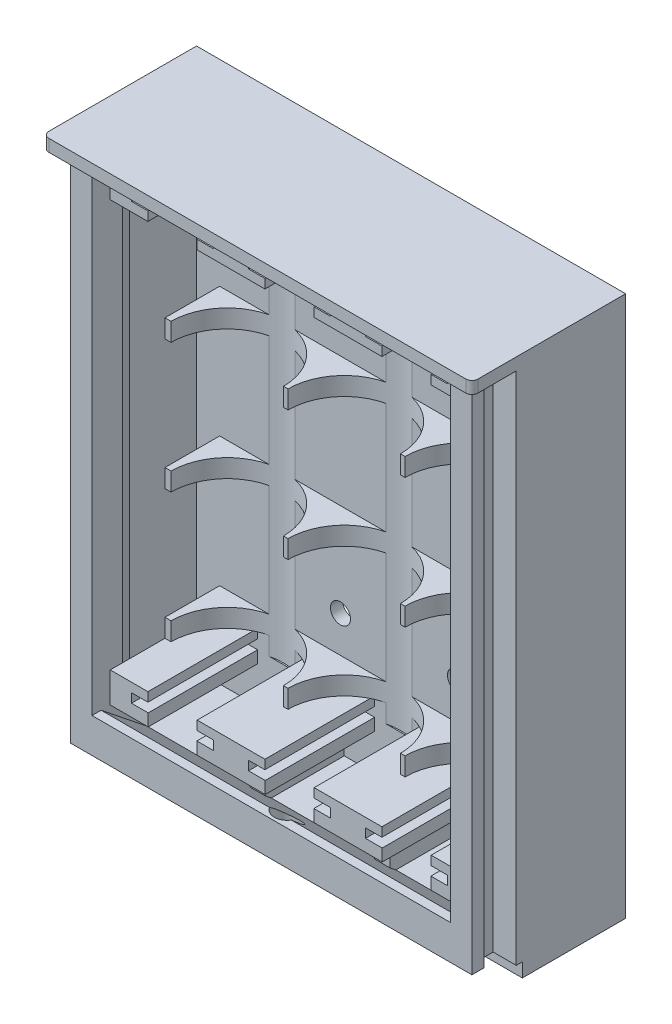
SolidWorks part; units mm, degrees
ref_plane "Ön Düzlem" through (0, 0, 0) normal (0, 0, 1) x (1, 0, 0)
ref_plane "Üst Düzlem" through (0, 0, 0) normal (0, 1, 0) x (1, 0, 0)
ref_plane "Sağ Düzlem" through (0, 0, 0) normal (1, 0, 0) x (0, 0, -1)
sketch "Çizim1" plane through (0, 0, 0) normal (0, 0, 1) x (1, 0, 0)
  line L1 (0, 0) -> (63, 0)
  line L2 (0, 0) -> (0, 85)
  line L3 (0, 85) -> (63, 85)
  line L4 (63, 0) -> (63, 85)
  dimension "D1" = 63
  dimension "D2" = 85
extrude "Yükseklik-Ekstrüzyon1" add sketch "Çizim1" along normal blind 2
sketch "Çizim2" plane through (0, 0, 2) normal (0, 0, 1) x (1, 0, 0)
  line L0 (2, 83) -> (2, 2)
  line L1 (2, 2) -> (61, 2)
  line L2 (61, 2) -> (61, 83)
  line L3 (61, 83) -> (2, 83)
  line L4 (0, 85) -> (0, 0)
  line L5 (0, 0) -> (63, 0)
  line L6 (63, 0) -> (63, 85)
  line L7 (63, 85) -> (0, 85)
  line L8 (0, 85) -> (0, 0)
  line L9 (0, 0) -> (63, 0)
  line L10 (63, 0) -> (63, 85)
  line L11 (63, 85) -> (0, 85)
  dimension "D1" = 0
  dimension "D2" = 2
extrude "Yükseklik-Ekstrüzyon2" add sketch "Çizim2" along normal blind 21
sketch "Çizim3" plane through (0, 0, 2) normal (0, 0, 1) x (1, 0, 0)
  line L0 (2, 83) -> (2, 2) construction
  line L1 (2, 81) -> (61, 81)
  line L2 (2, 81) -> (2, 79)
  line L3 (2, 79) -> (61, 79)
  line L4 (61, 81) -> (61, 79)
  line L5 (61, 2) -> (61, 83) construction
  line L6 (2, 42.5) -> (61, 42.5) construction
  line L7 (2, 83) -> (2, 2) construction
  line L8 (61, 2) -> (61, 83) construction
  line L9 (61, 83) -> (2, 83) construction
  line L10 (61, 4) -> (61, 6)
  line L11 (2, 6) -> (61, 6)
  line L12 (2, 4) -> (2, 6)
  line L13 (2, 4) -> (61, 4)
  dimension "D1" = 2
  dimension "D2" = 2
extrude "Yükseklik-Ekstrüzyon3" add sketch "Çizim3" along normal blind 18
sketch "Çizim4" plane through (0, 0, 2) normal (0, 0, 1) x (1, 0, 0)
  line L0 (61, 83) -> (2, 83) construction
  line L1 (20, 83) -> (22.5, 83)
  line L2 (20, 83) -> (20, 81)
  line L3 (20, 81) -> (22.5, 81)
  line L4 (22.5, 83) -> (22.5, 81)
  line L5 (61, 81) -> (2, 81) construction
  line L6 (61, 81) -> (61, 83) construction
  line L7 (40.5, 83) -> (43, 83)
  line L8 (40.5, 83) -> (40.5, 81)
  line L9 (40.5, 81) -> (43, 81)
  line L10 (43, 83) -> (43, 81)
  line L12 (2, 42.5) -> (61, 42.5) construction
  line L13 (2, 79) -> (2, 6) construction
  line L14 (61, 6) -> (61, 79) construction
  line L15 (43, 2) -> (43, 4)
  line L16 (40.5, 4) -> (43, 4)
  line L17 (40.5, 2) -> (40.5, 4)
  line L18 (40.5, 2) -> (43, 2)
  line L19 (22.5, 2) -> (22.5, 4)
  line L20 (20, 4) -> (22.5, 4)
  line L21 (20, 2) -> (20, 4)
  line L22 (20, 2) -> (22.5, 2)
  point P14 (61, 82)
  dimension "D1" = 2.5
  dimension "D2" = 2.5
  dimension "D3" = 18
  dimension "D4" = 18
extrude "Yükseklik-Ekstrüzyon4" add sketch "Çizim4" along normal up to vertex
ref_plane "Düzlem2" through (0, 79, 0) normal (0, -1, 0) x (-1, 0, 0)
sketch "Çizim5" plane through (0, 79, 0) normal (0, -1, 0) x (-1, 0, 0)
  line L0 (-12.25, -11) -> (-50.75, -11) construction
  line L1 (-31.5, -20) -> (-31.5, -11) construction
  line L2 (-2, -20) -> (-61, -20) construction
  line L4 (-2, -11) -> (-3, -11)
  line L5 (-2, -2) -> (-10.114, -2)
  line L6 (-2, -2) -> (-2, -11)
  line L7 (-40.75, -11) -> (-41.5, -11)
  line L8 (-61, -2) -> (-61, -11)
  line L9 (-21.5, -11) -> (-22.25, -11)
  line L10 (-60, -11) -> (-61, -11)
  line L11 (-61, -20) -> (-61, -2) construction
  line L12 (-33.636, -2) -> (-48.614, -2)
  line L13 (-14.386, -2) -> (-29.364, -2)
  line L14 (-52.886, -2) -> (-61, -2)
  arc A0 (-3, -11) -> (-10.114, -2) centre (-12.25, -11) ccw
  arc A1 (-22.25, -11) -> (-29.364, -2) centre (-31.5, -11) ccw
  arc A2 (-41.5, -11) -> (-48.614, -2) centre (-50.75, -11) ccw
  arc A3 (-14.386, -2) -> (-21.5, -11) centre (-12.25, -11) ccw
  arc A4 (-33.636, -2) -> (-40.75, -11) centre (-31.5, -11) ccw
  arc A5 (-52.886, -2) -> (-60, -11) centre (-50.75, -11) ccw
  point P7 (-31.5, -11)
  dimension "D2" = 18.5
  dimension "D1" = 9
  dimension "D3" = 38.5
extrude "Yükseklik-Ekstrüzyon5" add sketch "Çizim5" along normal up to vertex (73 mm away)
sketch "Çizim6" plane through (0, 79, 0) normal (0, -1, 0) x (1, 0, 0)
  circle A0 centre (12.25, 11) radius 9.25
  circle A1 centre (31.5, 11) radius 9.25
  circle A2 centre (50.75, 11) radius 9.25
  arc A3 (41.5, 11) -> (48.614, 2) centre (50.75, 11) ccw construction
  arc A4 (3, 11) -> (10.114, 2) centre (12.25, 11) ccw construction
  arc A5 (22.25, 11) -> (29.364, 2) centre (31.5, 11) ccw construction
extrude "Kes-Ekstrüzyon1" cut sketch "Çizim6" along normal up to vertex (73 mm away)
sketch "Çizim7" plane through (0, 0, 20) normal (0, 0, 1) x (1, 0, 0)
  line L0 (60, 6) -> (60, 79) construction
  line L1 (3, 79) -> (60, 79)
  line L2 (3, 79) -> (3, 76)
  line L3 (3, 76) -> (60, 76)
  line L4 (60, 79) -> (60, 76)
  line L5 (3, 6) -> (3, 79) construction
  line L6 (3, 6) -> (60, 6)
  line L7 (3, 6) -> (3, 9)
  line L8 (3, 9) -> (60, 9)
  line L9 (60, 6) -> (60, 9)
  line L10 (3, 30.3367) -> (60, 30.3367)
  line L11 (3, 30.3367) -> (3, 12)
  line L12 (3, 12) -> (60, 12)
  line L13 (60, 30.3367) -> (60, 12)
  line L15 (3, 73) -> (60, 73)
  line L16 (3, 73) -> (3, 54.6667)
  line L17 (3, 54.6667) -> (60, 54.6667)
  line L18 (60, 73) -> (60, 54.6667)
  line L19 (3, 51.6667) -> (60, 51.6667)
  line L20 (3, 51.6667) -> (3, 33.3367)
  line L21 (3, 33.3367) -> (60, 33.3367)
  line L22 (60, 51.6667) -> (60, 33.3367)
  dimension "D1" = 3
  dimension "D2" = 3
  dimension "D3" = 3
  dimension "D4" = 3
  dimension "D5" = 3
  dimension "D6" = 3
  dimension "D7" = 18.3333
  dimension "D8" = 18.33
extrude "Kes-Ekstrüzyon2" cut sketch "Çizim7" against normal blind 18
sketch "Çizim8" plane through (0, 0, 2) normal (0, 0, 1) x (1, 0, 0)
  line L0 (21.875, 73) -> (21.875, 12) construction
  line L1 (29.364, 73) -> (14.386, 73) construction
  line L2 (14.386, 12) -> (29.364, 12) construction
  line L3 (41.125, 73) -> (41.125, 12) construction
  line L4 (48.614, 73) -> (33.636, 73) construction
  line L5 (41.5, 12) -> (40.75, 12) construction
  line L6 (21.875, 67) -> (41.125, 67) construction
  line L7 (22.25, 73) -> (29.364, 73) construction
  line L8 (21.875, 42.5) -> (41.125, 42.5) construction
  circle A0 centre (21.875, 67) radius 1.65
  circle A1 centre (41.125, 67) radius 1.65
  circle A2 centre (41.125, 18) radius 1.65
  circle A3 centre (21.875, 18) radius 1.65
  dimension "D2" = 3.3
  dimension "D1" = 6
extrude "Kes-Ekstrüzyon3" cut sketch "Çizim8" against normal blind 18
sketch "Çizim9" plane through (0, 0, 20) normal (0, 0, 1) x (1, 0, 0)
  line L0 (48.614, 79) -> (33.636, 79) construction
  line L1 (5.5, 77.5) -> (8.2, 77.5)
  line L2 (2, 79) -> (2, 76)
  line L3 (2, 76) -> (8.2, 76)
  line L4 (8.2, 77.5) -> (8.2, 76)
  line L5 (10.114, 76) -> (3, 76) construction
  line L6 (2, 6) -> (2, 79) construction
  line L7 (5.5, 79) -> (5.5, 77.5)
  line L8 (10.114, 79) -> (3, 79) construction
  line L9 (5.5, 79) -> (2, 79)
  line L10 (10.114, 79) -> (14.386, 79) construction
  line L11 (19, 79) -> (21.25, 79)
  line L12 (29.364, 79) -> (14.386, 79) construction
  line L13 (21.25, 79) -> (21.25, 76)
  line L14 (14.386, 76) -> (29.364, 76) construction
  line L15 (21.25, 76) -> (16.3, 76)
  line L16 (16.3, 76) -> (16.3, 77.5)
  line L17 (16.3, 77.5) -> (19, 77.5)
  line L18 (19, 77.5) -> (19, 79)
  line L19 (2, 79) -> (61, 79) construction
  line L20 (10.114, 79) -> (14.386, 79) construction
  line L21 (12.25, 79) -> (12.25, 83) construction
  line L22 (14.386, 79) -> (14.386, 76) construction
  line L23 (20, 83) -> (2, 83) construction
  line L24 (21.25, 83) -> (21.25, 79) construction
  line L25 (22.5, 83) -> (20, 83) construction
  line L26 (24.75, 79) -> (21.25, 79)
  line L27 (21.25, 79) -> (21.25, 76)
  line L28 (21.25, 76) -> (27.45, 76)
  line L29 (27.45, 77.5) -> (27.45, 76)
  line L30 (24.75, 77.5) -> (27.45, 77.5)
  line L31 (24.75, 79) -> (24.75, 77.5)
  line L32 (35.55, 77.5) -> (38.25, 77.5)
  line L33 (35.55, 76) -> (35.55, 77.5)
  line L34 (41.75, 76) -> (35.55, 76)
  line L35 (41.75, 79) -> (41.75, 76)
  line L36 (38.25, 79) -> (41.75, 79)
  line L37 (38.25, 77.5) -> (38.25, 79)
  line L38 (44, 79) -> (41.75, 79)
  line L39 (41.75, 79) -> (41.75, 76)
  line L40 (41.75, 76) -> (46.7, 76)
  line L41 (46.7, 77.5) -> (46.7, 76)
  line L42 (44, 77.5) -> (46.7, 77.5)
  line L43 (44, 79) -> (44, 77.5)
  line L44 (54.8, 77.5) -> (57.5, 77.5)
  line L45 (54.8, 76) -> (54.8, 77.5)
  line L46 (61, 76) -> (54.8, 76)
  line L47 (61, 79) -> (61, 76)
  line L48 (57.5, 79) -> (61, 79)
  line L49 (57.5, 77.5) -> (57.5, 79)
  line L50 (61, 6) -> (61, 79) construction
  line L51 (41.75, 83) -> (41.75, 79) construction
  line L52 (43, 83) -> (40.5, 83) construction
  line L53 (50.75, 79) -> (50.75, 76.4277) construction
  line L54 (48.614, 79) -> (52.886, 79) construction
  line L55 (31.5, 79) -> (31.5, 81.9834) construction
  line L56 (29.364, 79) -> (33.636, 79) construction
  line L57 (35.55, 76) -> (41.75, 76)
  line L58 (38.25, 79) -> (41.75, 79)
  line L59 (41.75, 79) -> (38.25, 79)
  line L60 (0, 42.5) -> (63, 42.5) construction
  line L61 (0, 85) -> (0, 0) construction
  line L62 (63, 0) -> (63, 85) construction
  line L63 (31.5, 6) -> (31.5, 3.0166) construction
  line L64 (10.114, 6) -> (14.386, 6) construction
  line L65 (41.75, 6) -> (38.25, 6)
  line L66 (38.25, 6) -> (41.75, 6)
  line L67 (35.55, 9) -> (41.75, 9)
  line L68 (57.5, 7.5) -> (57.5, 6)
  line L69 (57.5, 6) -> (61, 6)
  line L70 (61, 6) -> (61, 9)
  line L71 (61, 9) -> (54.8, 9)
  line L72 (54.8, 9) -> (54.8, 7.5)
  line L73 (54.8, 7.5) -> (57.5, 7.5)
  line L74 (44, 6) -> (44, 7.5)
  line L75 (44, 7.5) -> (46.7, 7.5)
  line L76 (46.7, 7.5) -> (46.7, 9)
  line L77 (41.75, 9) -> (46.7, 9)
  line L78 (41.75, 6) -> (41.75, 9)
  line L79 (44, 6) -> (41.75, 6)
  line L80 (38.25, 7.5) -> (38.25, 6)
  line L81 (38.25, 6) -> (41.75, 6)
  line L82 (41.75, 6) -> (41.75, 9)
  line L83 (41.75, 9) -> (35.55, 9)
  line L84 (35.55, 9) -> (35.55, 7.5)
  line L85 (35.55, 7.5) -> (38.25, 7.5)
  line L86 (24.75, 6) -> (24.75, 7.5)
  line L87 (24.75, 7.5) -> (27.45, 7.5)
  line L88 (27.45, 7.5) -> (27.45, 9)
  line L89 (21.25, 9) -> (27.45, 9)
  line L90 (21.25, 6) -> (21.25, 9)
  line L91 (24.75, 6) -> (21.25, 6)
  line L92 (19, 7.5) -> (19, 6)
  line L93 (16.3, 7.5) -> (19, 7.5)
  line L94 (16.3, 9) -> (16.3, 7.5)
  line L95 (21.25, 9) -> (16.3, 9)
  line L96 (21.25, 6) -> (21.25, 9)
  line L97 (19, 6) -> (21.25, 6)
  line L98 (5.5, 6) -> (2, 6)
  line L99 (5.5, 6) -> (5.5, 7.5)
  line L100 (8.2, 7.5) -> (8.2, 9)
  line L101 (2, 9) -> (8.2, 9)
  line L102 (2, 6) -> (2, 9)
  line L103 (5.5, 7.5) -> (8.2, 7.5)
  line L104 (16.3, 9) -> (21.25, 9)
  point P67 (57.5, 78.25)
  point P71 (27.45, 76.75)
  point P72 (35.55, 76.75)
  line M38 (2, 79) -> (61, 79)
  dimension "D1" = 8.1
  dimension "D2" = 13.5
  dimension "D3" = 1.5
  dimension "D4" = 8.1
  dimension "D5" = 8.1
  dimension "D6" = 13.5
  dimension "D7" = 13.5
extrude "Yükseklik-Ekstrüzyon7" add sketch "Çizim9" against normal blind 18 contours L99 L103 L100 L101 L102 L98 | L92 L97 L90 L95 L94 L93 | L91 L86 L87 L88 L89 L90 | L84 L85 L80 L65 L78 L67 | L79 L74 L75 L76 L77 L78 | L72 L73 L68 L69 L70 L71 | L7 L2 L3 L4 L1 M38 | L18 L17 L16 L15 L13 M38 | L31 L13 L28 L29 L30 M38 | L37 L32 L33 L34 L35 M38 | L43 L35 L40 L41 L42 M38 | L49 L44 L45 L46 L47 M38
sketch "Çizim10" plane through (0, 0, 20) normal (0, 0, 1) x (1, 0, 0)
  line L0 (20, 81) -> (2, 81) construction
  line L1 (8.25, 81) -> (16.25, 81)
  line L2 (8.25, 81) -> (8.25, 79)
  line L3 (8.25, 79) -> (16.25, 79)
  line L4 (16.25, 81) -> (16.25, 79)
  line L5 (19, 79) -> (14.386, 79) construction
  line L6 (10.114, 73) -> (14.386, 73) construction
  line L7 (12.25, 73) -> (12.25, 75.7871) construction
  line L8 (29.364, 73) -> (33.636, 73) construction
  line L9 (48.614, 73) -> (52.886, 73) construction
  line L10 (31.5, 73) -> (31.5, 74.6684) construction
  line L11 (50.75, 73) -> (50.75, 74.6684) construction
  line L12 (40.5, 81) -> (22.5, 81) construction
  line L13 (27.5, 81) -> (35.5, 81)
  line L14 (27.5, 81) -> (27.5, 79)
  line L15 (27.5, 79) -> (35.5, 79)
  line L16 (35.5, 81) -> (35.5, 79)
  line L17 (38.25, 79) -> (33.636, 79) construction
  line L18 (61, 81) -> (43, 81) construction
  line L19 (46.75, 81) -> (54.75, 81)
  line L20 (46.75, 81) -> (46.75, 79)
  line L21 (46.75, 79) -> (54.75, 79)
  line L22 (54.75, 81) -> (54.75, 79)
  line L23 (57.5, 79) -> (52.886, 79) construction
  line L24 (0, 42.5) -> (63, 42.5) construction
  line L25 (0, 85) -> (0, 0) construction
  line L26 (63, 0) -> (63, 85) construction
  line L27 (54.75, 4) -> (54.75, 6)
  line L28 (46.75, 6) -> (54.75, 6)
  line L29 (46.75, 4) -> (46.75, 6)
  line L30 (46.75, 4) -> (54.75, 4)
  line L31 (35.5, 4) -> (35.5, 6)
  line L32 (27.5, 6) -> (35.5, 6)
  line L33 (27.5, 4) -> (27.5, 6)
  line L34 (27.5, 4) -> (35.5, 4)
  line L35 (16.25, 4) -> (16.25, 6)
  line L36 (8.25, 6) -> (16.25, 6)
  line L37 (8.25, 4) -> (8.25, 6)
  line L38 (8.25, 4) -> (16.25, 4)
  dimension "D1" = 8
  dimension "D2" = 8
  dimension "D3" = 8
extrude "Kes-Ekstrüzyon4" cut sketch "Çizim10" against normal up to vertex
sketch "Çizim11" plane through (0, 0, 20) normal (0, 0, 1) x (1, 0, 0)
  line L0 (61, 83) -> (2, 83) construction
  line L1 (20, 83) -> (22.5, 83)
  line L2 (20, 83) -> (20, 81)
  line L3 (20, 81) -> (22.5, 81)
  line L4 (22.5, 83) -> (22.5, 81)
  line L5 (40.5, 83) -> (43, 83)
  line L6 (40.5, 83) -> (40.5, 81)
  line L7 (40.5, 81) -> (43, 81)
  line L8 (43, 83) -> (43, 81)
  line L9 (40.5, 83) -> (22.5, 83) construction
  line L10 (40.5, 83) -> (40.5, 81) construction
  line L11 (0, 42.5) -> (63, 42.5) construction
  line L12 (0, 85) -> (0, 0) construction
  line L13 (63, 0) -> (63, 85) construction
  line L14 (43, 2) -> (43, 4)
  line L15 (40.5, 4) -> (43, 4)
  line L16 (40.5, 2) -> (40.5, 4)
  line L17 (40.5, 2) -> (43, 2)
  line L18 (22.5, 2) -> (22.5, 4)
  line L19 (20, 4) -> (22.5, 4)
  line L20 (20, 2) -> (20, 4)
  line L21 (20, 2) -> (22.5, 2)
extrude "Kes-Ekstrüzyon5" cut sketch "Çizim11" against normal blind 5
sketch "Çizim12" plane through (0, 0, 11) normal (0, 0, 1) x (1, 0, 0)
  line L0 (2, 83) -> (2, 2) construction
  line L1 (3, 73) -> (2, 73)
  line L2 (3, 73) -> (3, 54.6667)
  line L3 (3, 54.6667) -> (2, 54.6667)
  line L4 (2, 73) -> (2, 54.6667)
  line L5 (3, 30.3367) -> (3, 12) construction
  line L6 (3, 51.6667) -> (2, 51.6667)
  line L7 (3, 51.6667) -> (3, 33.3367)
  line L8 (3, 33.3367) -> (2, 33.3367)
  line L9 (2, 51.6667) -> (2, 33.3367)
  line L10 (3, 30.3367) -> (2, 30.3367)
  line L11 (3, 30.3367) -> (3, 12)
  line L12 (3, 12) -> (2, 12)
  line L13 (2, 30.3367) -> (2, 12)
  line L14 (10.114, 30.3367) -> (3, 30.3367) construction
  line L15 (2, 9) -> (2, 76) construction
  line L16 (3, 12) -> (10.114, 12) construction
  line L17 (3, 33.3367) -> (10.114, 33.3367) construction
  line L18 (3, 54.6667) -> (10.114, 54.6667) construction
  line L19 (31.5, 85) -> (31.5, 0) construction
  line L20 (63, 85) -> (0, 85) construction
  line L21 (0, 0) -> (63, 0) construction
  line L22 (61, 30.3367) -> (61, 12)
  line L23 (60, 12) -> (61, 12)
  line L24 (60, 30.3367) -> (60, 12)
  line L25 (60, 30.3367) -> (61, 30.3367)
  line L26 (61, 51.6667) -> (61, 33.3367)
  line L27 (60, 33.3367) -> (61, 33.3367)
  line L28 (60, 51.6667) -> (60, 33.3367)
  line L29 (60, 51.6667) -> (61, 51.6667)
  line L30 (61, 73) -> (61, 54.6667)
  line L31 (60, 54.6667) -> (61, 54.6667)
  line L32 (60, 73) -> (60, 54.6667)
  line L33 (60, 73) -> (61, 73)
extrude "Kes-Ekstrüzyon6" cut sketch "Çizim12" against normal up to vertex (9 mm away)
sketch "Çizim13" plane through (0, 0, 0) normal (0, -1, 0) x (1, 0, 0)
  line L0 (31.5, 23) -> (31.5, 0) construction
  line L1 (0, 23) -> (-1.5, 23)
  line L2 (0, 23) -> (0, 21)
  line L3 (0, 21) -> (-1.5, 21)
  line L4 (-1.5, 23) -> (-1.5, 21)
  line L5 (0, 23) -> (63, 23) construction
  line L6 (0, 0) -> (63, 0) construction
  line L7 (64.5, 23) -> (64.5, 21)
  line L8 (63, 21) -> (64.5, 21)
  line L9 (63, 23) -> (63, 21)
  line L10 (63, 23) -> (64.5, 23)
  dimension "D1" = 1.5
  dimension "D2" = 2
extrude "Yükseklik-Ekstrüzyon8" add sketch "Çizim13" against normal up to vertex (85 mm away)
sketch "Çizim14" plane through (0, 0, 23) normal (0, 0, 1) x (1, 0, 0)
  line L0 (64.5, 85) -> (64.5, 0) construction
  line L1 (-1.5, 85) -> (64.5, 85)
  line L2 (-1.5, 85) -> (-1.5, 83)
  line L3 (-1.5, 83) -> (64.5, 83)
  line L4 (64.5, 85) -> (64.5, 83)
  line L5 (61, 83) -> (43, 83) construction
extrude "Yükseklik-Ekstrüzyon9" add sketch "Çizim14" along normal blind 2.3
sketch "Çizim15" plane through (0, 85, 0) normal (0, 1, 0) x (1, 0, 0)
  line L1 (64.5, -25.3) -> (65.5, -25.3)
  line L2 (64.5, -25.3) -> (64.5, -21)
  line L4 (66.5, -24.3) -> (66.5, -20.35)
  line L5 (63, -21) -> (63, 0) construction
  line L6 (64.5, -21) -> (63, -21)
  line L7 (64.5, -18.35) -> (63, -18.35)
  line L8 (63, -21) -> (63, -18.35)
  line L9 (31.5, -25.3) -> (31.5, 0) construction
  line L10 (64.5, -25.3) -> (-1.5, -25.3) construction
  line L11 (63, 0) -> (0, 0) construction
  line L12 (0, -21) -> (0, -18.35)
  line L13 (-1.5, -18.35) -> (0, -18.35)
  line L14 (-1.5, -21) -> (0, -21)
  line L15 (-3.5, -24.3) -> (-3.5, -20.35)
  line L16 (-1.5, -25.3) -> (-1.5, -21)
  line L17 (-1.5, -25.3) -> (-2.5, -25.3)
  arc A0 (64.5, -18.35) -> (66.5, -20.35) centre (64.5, -20.35) cw
  arc A1 (66.5, -24.3) -> (65.5, -25.3) centre (65.5, -24.3) cw
  arc A2 (-3.5, -24.3) -> (-2.5, -25.3) centre (-2.5, -24.3) ccw
  arc A3 (-1.5, -18.35) -> (-3.5, -20.35) centre (-1.5, -20.35) ccw
  point P10 (66.5, -25.3)
  point P31 (-3.5, -25.3)
  dimension "D3" = 2
  dimension "D4" = 1
  dimension "D1" = 2
  dimension "D2" = 2.65
extrude "Yükseklik-Ekstrüzyon10" add sketch "Çizim15" against normal up to vertex
sketch "Çizim16" plane through (0, 85, 0) normal (0, 1, 0) x (1, 0, 0)
  line L0 (63, 0) -> (66.8, 0)
  line L1 (66.8, 0) -> (66.8, -18)
  line L2 (66.8, -18) -> (63, -18)
  line L3 (63, -18.35) -> (63, 0) construction
  line L4 (63, -18) -> (63, 0)
  line L5 (63, 0) -> (62.9308, 0.0549)
  line L6 (31.5, 0) -> (31.5, -25.3) construction
  line L7 (63, 0) -> (0, 0) construction
  line L8 (65.5, -25.3) -> (-2.5, -25.3) construction
  line L9 (0, 0) -> (0.0692, 0.0549)
  line L10 (0, -18) -> (0, 0)
  line L11 (-3.8, -18) -> (0, -18)
  line L12 (-3.8, 0) -> (-3.8, -18)
  line L13 (0, 0) -> (-3.8, 0)
  dimension "D1" = 3.8
  dimension "D2" = 18
extrude "Yükseklik-Ekstrüzyon11" add sketch "Çizim16" against normal blind 85 contours L0 L1 L2 L4 | L13 L12 L11 L10
sketch "Çizim17" plane through (0, 85, 0) normal (0, 1, 0) x (1, 0, 0)
  line L0 (65.5, -25.3) -> (-2.5, -25.3) construction
  line L1 (66.8, -18) -> (63, -18)
  line L2 (66.8, -18) -> (66.8, -24.3)
  line L3 (65.8, -25.3) -> (63, -25.3)
  line L4 (63, -18) -> (63, -25.3)
  line L5 (63, -18.35) -> (63, -18) construction
  line L6 (31.5, -25.3) -> (31.5, 0) construction
  line L7 (66.8, 0) -> (-3.8, 0) construction
  line L8 (0, -18) -> (0, -25.3)
  line L9 (-2.8, -25.3) -> (0, -25.3)
  line L10 (-3.8, -18) -> (-3.8, -24.3)
  line L11 (-3.8, -18) -> (0, -18)
  arc A0 (66.8, -24.3) -> (65.8, -25.3) centre (65.8, -24.3) cw
  arc A1 (-3.8, -24.3) -> (-2.8, -25.3) centre (-2.8, -24.3) ccw
  dimension "D1" = 1
extrude "Yükseklik-Ekstrüzyon12" add sketch "Çizim17" against normal up to vertex
sketch "Çizim18" plane through (0, 76, 0) normal (0, -1, 0) x (1, 0, 0)
  line L0 (2, 18) -> (-1.8, 13)
  line L1 (2, 11) -> (2, 20) construction
  line L2 (-1.8, 13) -> (-1.8, 2)
  line L3 (-1.8, 2) -> (2, 2)
  line L4 (2, 2) -> (2, 18)
  line L5 (2, 20) -> (8.2, 20) construction
  line L6 (-3.8, 0) -> (-3.8, 24.3) construction
  line L7 (31.5, 25.3) -> (31.5, 0) construction
  line L8 (-2.8, 25.3) -> (65.8, 25.3) construction
  line L9 (66.8, 0) -> (-3.8, 0) construction
  line L10 (61, 2) -> (61, 18)
  line L11 (64.8, 2) -> (61, 2)
  line L12 (64.8, 13) -> (64.8, 2)
  line L13 (61, 18) -> (64.8, 13)
  dimension "D1" = 5
  dimension "D2" = 2
  dimension "D3" = 2
extrude "Kes-Ekstrüzyon7" cut sketch "Çizim18" along normal up to vertex and the other way up to vertex
sketch "Çizim19" plane through (0, 0, 0) normal (0, -1, 0) x (1, 0, 0)
  line L12 (-3.8, 0) -> (66.8, 0)
  line L13 (66.8, 0) -> (66.8, 18)
  line L14 (66.8, 18) -> (63, 18)
  line L15 (63, 18) -> (63, 21)
  line L16 (63, 21) -> (64.5, 21)
  line L17 (64.5, 21) -> (64.5, 23)
  line L18 (64.5, 23) -> (-1.5, 23)
  line L19 (-1.5, 23) -> (-1.5, 21)
  line L20 (-1.5, 21) -> (0, 21)
  line L21 (0, 21) -> (0, 18)
  line L22 (0, 18) -> (-3.8, 18)
  line L23 (-3.8, 18) -> (-3.8, 0)
  line L24 (-3.8, 0) -> (66.8, 0)
  line L25 (66.8, 0) -> (66.8, 18)
  line L26 (66.8, 18) -> (63, 18)
  line L27 (63, 18) -> (63, 21)
  line L28 (63, 21) -> (64.5, 21)
  line L29 (64.5, 21) -> (64.5, 23)
  line L30 (64.5, 23) -> (-1.5, 23)
  line L31 (-1.5, 23) -> (-1.5, 21)
  line L32 (-1.5, 21) -> (0, 21)
  line L33 (0, 21) -> (0, 18)
  line L34 (0, 18) -> (-3.8, 18)
  line L35 (-3.8, 18) -> (-3.8, 0)
  dimension "D1" = 0
extrude "Yükseklik-Ekstrüzyon13" add sketch "Çizim19" along normal blind 4
sketch "Çizim20" plane through (2, 0, 0) normal (1, 0, 0) x (0, 0, -1)
  line L0 (-19, 2) -> (-14, -2)
  line L1 (-23, 2) -> (-18, 2) construction
  line L2 (-14, -2) -> (-2, -2)
  line L3 (-2, -2) -> (-2, 2)
  line L4 (-2, 2) -> (-19, 2)
  line L5 (-18, -4) -> (0, -4) construction
  line L6 (-23, 83) -> (-23, -4) construction
  dimension "D1" = 2
  dimension "D2" = 5
  dimension "D3" = 4
extrude "Kes-Ekstrüzyon8" cut sketch "Çizim20" along normal up to vertex
sketch "Çizim21" plane through (0, 2, 0) normal (0, -1, 0) x (1, 0, 0)
  line L4 (43, 2) -> (43, 15)
  line L5 (43, 15) -> (40.5, 15)
  line L6 (40.5, 15) -> (40.5, 2)
  line L7 (40.5, 2) -> (43, 2)
  line L8 (43, 2) -> (43, 15)
  line L9 (43, 15) -> (40.5, 15)
  line L10 (40.5, 15) -> (40.5, 2)
  line L11 (40.5, 2) -> (43, 2)
  line L12 (22.5, 2) -> (22.5, 15)
  line L13 (22.5, 15) -> (20, 15)
  line L14 (20, 15) -> (20, 2)
  line L15 (20, 2) -> (22.5, 2)
  line L16 (22.5, 2) -> (22.5, 15)
  line L17 (22.5, 15) -> (20, 15)
  line L18 (20, 15) -> (20, 2)
  line L19 (20, 2) -> (22.5, 2)
  dimension "D1" = 0
  dimension "D2" = 0
extrude "Yükseklik-Ekstrüzyon14" add sketch "Çizim21" along normal up to vertex (4 mm away)
sketch "Çizim22" plane through (0, -4, 0) normal (0, -1, 0) x (1, 0, 0)
  line L0 (-3.8, 20.4) -> (66.8, 20.4) construction
  line L1 (66.8, 0) -> (66.8, 18) construction
  line L2 (-3.8, 18) -> (-3.8, 0) construction
  line L3 (-2.8, 25.3) -> (65.8, 25.3) construction
  circle A0 centre (31.5, 20.4) radius 2.1
  dimension "D2" = 4.2
  dimension "D1" = 4.9
extrude "Kes-Ekstrüzyon9" cut sketch "Çizim22" against normal up to vertex
sketch "Çizim23" plane through (0, -4, 0) normal (0, -1, 0) x (1, 0, 0)
  line L0 (66.8, 24.3) -> (66.8, 18) construction
  line L1 (-3.8, 17) -> (66.8, 17)
  line L2 (-3.8, 17) -> (-3.8, 25.3)
  line L3 (-3.8, 25.3) -> (66.8, 25.3)
  line L4 (66.8, 17) -> (66.8, 25.3)
  line L5 (-2.8, 25.3) -> (65.8, 25.3) construction
  line L6 (0, 18) -> (-3.8, 18) construction
  line L7 (-3.8, 18) -> (-3.8, 24.3) construction
  dimension "D1" = 1
extrude "Kes-Ekstrüzyon10" cut sketch "Çizim23" against normal blind 2.3
sketch "Çizim24" plane through (2, 0, 0) normal (1, 0, 0) x (0, 0, -1)
  line L0 (-23, 2) -> (-23, 4)
  line L1 (-23, 83) -> (-23, 2) construction
  line L2 (-23, 4) -> (-21.5, 4)
  line L3 (-21.5, 4) -> (-19, 2)
  line L4 (-19, 2) -> (-23, 2)
  line L6 (-14, -2) -> (-19, 2) construction
  dimension "D1" = 2
extrude "Yükseklik-Ekstrüzyon15" add sketch "Çizim24" along normal up to vertex (59 mm away)
sketch "Çizim25" plane through (0, 2, 0) normal (0, -1, 0) x (1, 0, 0)
  line L1 (29.9348, 19) -> (33.0652, 19)
  line L2 (29.9348, 19) -> (33.0652, 19)
  arc A1 (33.0652, 19) -> (29.9348, 19) centre (31.5, 20.4) ccw
  arc A2 (33.0652, 19) -> (29.9348, 19) centre (31.5, 20.4) ccw
  dimension "D1" = 0
extrude "Kes-Ekstrüzyon11" cut sketch "Çizim25" against normal blind 2.3
